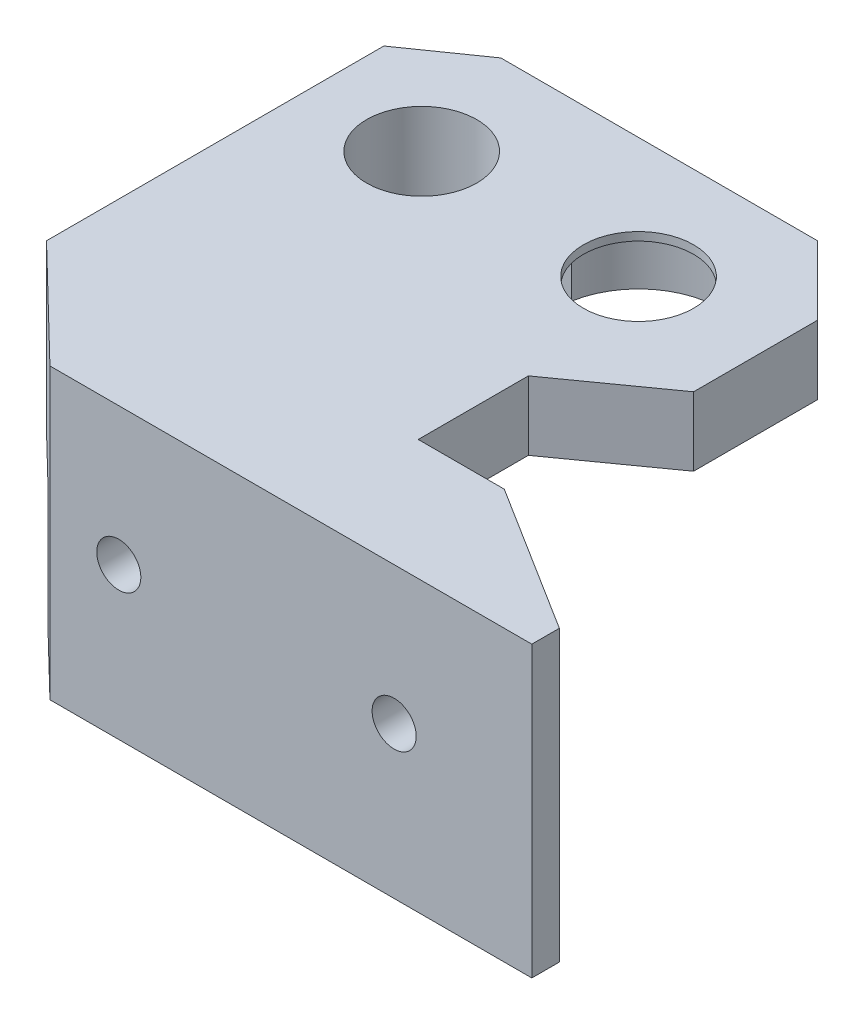
SolidWorks part; units mm, degrees
ref_plane "Front Plane" through (0, 0, 0) normal (0, 0, 1) x (1, 0, 0)
ref_plane "Top Plane" through (0, 0, 0) normal (0, 1, 0) x (1, 0, 0)
ref_plane "Right Plane" through (0, 0, 0) normal (1, 0, 0) x (0, 0, -1)
sketch "Sketch1" plane through (0, 0, 0) normal (0, 1, 0) x (1, 0, 0)
  line L0 (0, 0) -> (15.75, 0) construction
  line L5 (-4.25, 8.75) -> (18.75, 8.75)
  line L6 (18.75, 8.75) -> (23.75, 5.25)
  line L7 (23.75, 5.25) -> (23.75, -19.25)
  line L8 (23.75, -19.25) -> (15.75, -27)
  line L9 (15.75, -27) -> (-19.25, -27)
  line L10 (-19.25, -27) -> (-19.25, -25)
  line L11 (-19.25, -25) -> (-8.5, -18.25)
  line L12 (-8.5, -18.25) -> (-2.25, -18.25)
  line L13 (-2.25, -18.25) -> (-2.25, -10.25)
  line L14 (-2.25, -10.25) -> (-9.25, -5.25)
  line L15 (-9.25, -5.25) -> (-9.25, 3.75)
  line L16 (-9.25, 3.75) -> (-4.25, 8.75)
  line L17 (15.75, 0) -> (23.75, 0) construction
  circle A0 centre (0, 0) radius 4
  circle A1 centre (15.75, 0) radius 4
  point P0 (0, 0)
  dimension "D2" = 8
  dimension "D3" = 8
  dimension "D1" = 15.75
  dimension "D4" = 23
  dimension "D5" = 5
  dimension "D6" = 3.5
  dimension "D7" = 24.5
  dimension "D8" = 8
  dimension "D9" = 8.75
  dimension "D10" = 5
  dimension "D11" = 5
  dimension "D12" = 7
  dimension "D13" = 5
  dimension "D14" = 9
  dimension "D15" = 8
  dimension "D16" = 7.75
  dimension "D17" = 35
  dimension "D18" = 6.25
  dimension "D19" = 6.75
  dimension "D20" = 2
extrude "Boss-Extrude1" add sketch "Sketch1" along normal blind 5
sketch "Sketch2" plane through (0, 0, 0) normal (0, -1, 0) x (1, 0, 0)
  line L0 (23.75, 19.25) -> (23.75, -5.25)
  line L1 (23.75, -5.25) -> (20.25, -5.25)
  line L2 (20.25, -5.25) -> (20.25, 18.25)
  line L3 (20.25, 18.25) -> (-8.5, 18.25)
  line L4 (-8.5, 18.25) -> (-14.8704, 22.25)
  line L5 (-8.5, 18.25) -> (-19.25, 25) construction
  line L6 (-14.8704, 22.25) -> (20.6532, 22.25)
  line L7 (15.75, 27) -> (23.75, 19.25) construction
  line L8 (20.6532, 22.25) -> (23.75, 19.25)
  dimension "D1" = 3.5
  dimension "D2" = 4
extrude "Boss-Extrude2" add sketch "Sketch2" along normal blind 7
sketch "Sketch3" plane through (0, 0, 0) normal (0, -1, 0) x (1, 0, 0)
  line L5 (-14.8704, 22.25) -> (20.6532, 22.25)
  line L6 (20.6532, 22.25) -> (15.75, 27)
  line L7 (15.75, 27) -> (-19.25, 27)
  line L8 (-19.25, 27) -> (-19.25, 25)
  line L9 (-19.25, 25) -> (-14.8704, 22.25)
  line L10 (-14.8704, 22.25) -> (20.6532, 22.25)
  line L11 (20.6532, 22.25) -> (15.75, 27)
  line L12 (15.75, 27) -> (-19.25, 27)
  line L13 (-19.25, 27) -> (-19.25, 25)
  line L14 (-19.25, 25) -> (-14.8704, 22.25)
  dimension "D1" = 0
extrude "Boss-Extrude3" add sketch "Sketch3" along normal blind 16
sketch "Sketch6" plane through (0, 0, 0) normal (0, -1, 0) x (1, 0, 0)
  circle A0 centre (15.75, 0) radius 7
  circle A1 centre (15.75, 0) radius 4
  dimension "D1" = 14
extrude "Boss-Extrude4" add sketch "Sketch6" along normal blind 2.5
sketch "Sketch4" plane through (0, 0, 0) normal (0, -1, 0) x (1, 0, 0)
  line L0 (0, 0) -> (12.25, 0) construction
  line L1 (5.8838, -1) -> (12.3959, -1)
  line L2 (5.8838, 1) -> (12.3959, 1)
  line L3 (0, -1) -> (15.75, -1) construction
  line L4 (0, 1) -> (15.75, 1) construction
  line L5 (0, 0) -> (15.75, 0) construction
  arc A0 (5.8838, 1) -> (5.8838, -1) centre (0, 0) ccw
  arc A2 (12.3959, 1) -> (12.3959, -1) centre (15.75, 0) ccw
  dimension "D1" = 1
  dimension "D2" = 1
extrude "Cut-Extrude1" cut sketch "Sketch4" against normal blind 4.4
sketch "Sketch7" plane through (0, 4.4, 0) normal (0, -1, 0) x (1, 0, 0)
  line L2 (5.8838, -1) -> (11.877, -1)
  line L3 (11.877, 1) -> (5.8838, 1)
  line L4 (5.8838, -1) -> (11.877, -1)
  line L5 (11.877, 1) -> (5.8838, 1)
  arc A2 (5.8838, 1) -> (5.8838, -1) centre (0, 0) ccw
  arc A3 (11.877, 1) -> (11.877, -1) centre (15.75, 0) ccw
  arc A4 (5.8838, 1) -> (5.8838, -1) centre (0, 0) ccw
  arc A5 (11.877, 1) -> (11.877, -1) centre (15.75, 0) ccw
  dimension "D1" = 0
extrude "Cut-Extrude2" cut sketch "Sketch7" along normal through all
sketch "Sketch8" plane through (0, 0, 27) normal (0, 0, 1) x (1, 0, 0)
  line L0 (10.75, -5) -> (-9.25, -5) construction
  line L1 (-19.25, 5) -> (15.75, 5) construction
  line L2 (-19.25, 5) -> (-19.25, -16) construction
  circle A0 centre (10.75, -5) radius 1.6
  circle A1 centre (-9.25, -5) radius 1.6
  dimension "D1" = 3.2
  dimension "D2" = 3.2
  dimension "D3" = 20
  dimension "D4" = 10
  dimension "D5" = 10
extrude "Cut-Extrude3" cut sketch "Sketch8" against normal through all
sketch "Sketch9" plane through (0, 0, 18.25) normal (0, 0, -1) x (-1, 0, 0)
  circle A0 centre (-10.75, -5) radius 3
  circle A1 centre (9.25, -5) radius 3
  dimension "D1" = 6
  dimension "D2" = 6
extrude "Cut-Extrude4" cut sketch "Sketch9" against normal blind 4
mirror "Mirror1" about plane through (-19.25, 5, 27) normal (1, 0, 0) of "Boss-Extrude2", "Boss-Extrude4", "Cut-Extrude2", "Cut-Extrude3", "Cut-Extrude1", "Boss-Extrude3", "Boss-Extrude1", "Cut-Extrude4"
sketch "Sketch10" plane through (0, 5, 0) normal (0, 1, 0) x (1, 0, 0)
  line L0 (18.75, 8.75) -> (-4.25, 8.75) construction
  line L1 (30.4721, -27) -> (-19.25, -27)
  line L2 (30.4721, -27) -> (30.4721, 8.75)
  line L3 (30.4721, 8.75) -> (-19.25, 8.75)
  line L4 (-19.25, -27) -> (-19.25, 8.75)
  line L5 (30.4721, -27) -> (-19.25, 8.75) construction
  line L6 (30.4721, 8.75) -> (-19.25, -27) construction
  line L7 (15.75, -27) -> (-54.25, -27) construction
  point P0 (5.611, -9.125)
extrude "Cut-Extrude5" cut sketch "Sketch10" against normal through all
